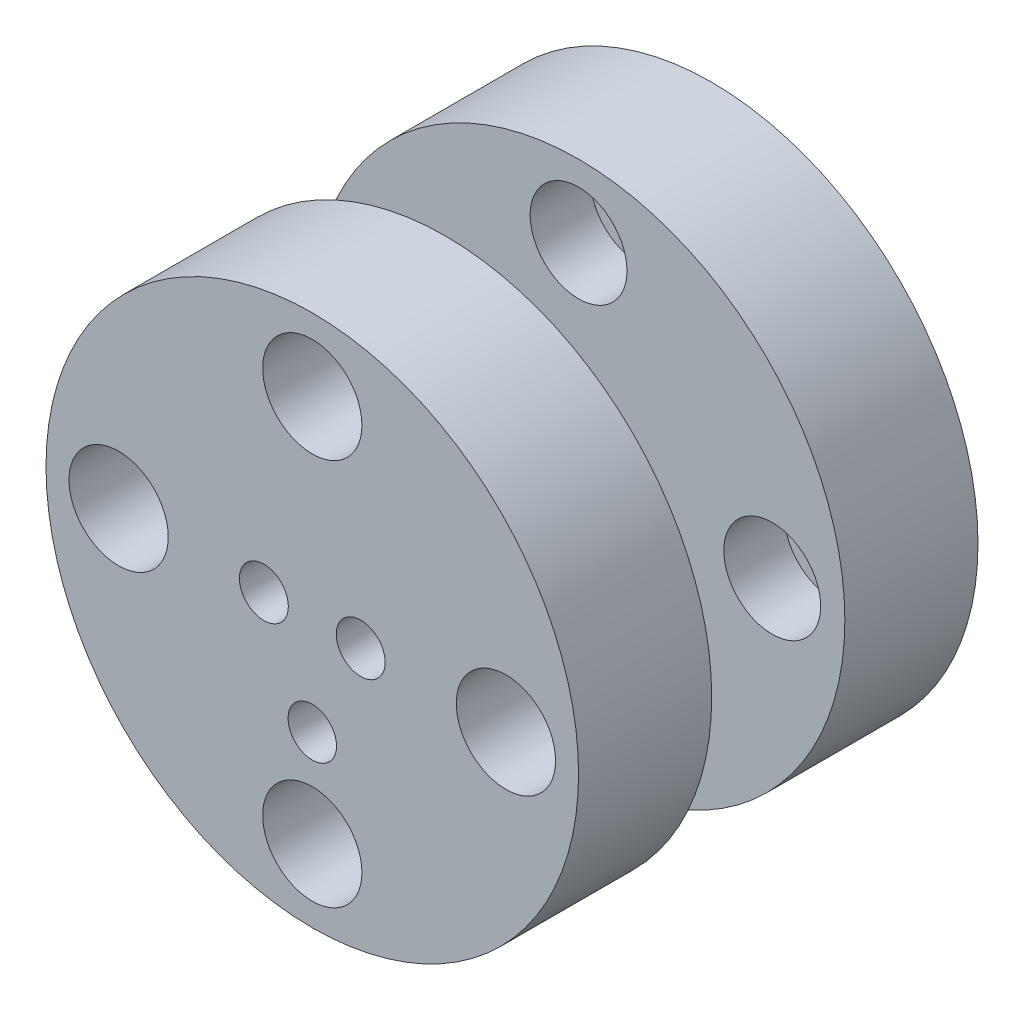
SolidWorks part; units mm, degrees
material "ﾎﾟﾘｵｷｼﾒﾁﾚﾝ(POM)ｱｾﾀｰﾙ共重合体"
ref_plane "正面" through (0, 0, 0) normal (0, 0, 1) x (1, 0, 0)
ref_plane "平面" through (0, 0, 0) normal (0, 1, 0) x (1, 0, 0)
ref_plane "右側面" through (0, 0, 0) normal (1, 0, 0) x (0, 0, -1)
sketch "ｽｹｯﾁ1" plane through (0, 0, 0) normal (0, 0, 1) x (1, 0, 0)
  line L0 (0, 0) -> (-8, 0) construction
  circle A0 centre (-8, 0) radius 1.15
  circle A1 centre (0, 8) radius 1.15
  circle A2 centre (8, 0) radius 1.15
  circle A3 centre (0, -8) radius 1.15
  circle A4 centre (0, 0) radius 11
  circle A5 centre (0, 0) radius 3 construction
  point P13 (0, 0)
  dimension "D1" = 2.3
  dimension "D4" = 8
  dimension "D5" = 6
  dimension "D2" = 8
  dimension "D3" = 4
extrude "ﾎﾞｽ - 押し出し1" add sketch "ｽｹｯﾁ1" along normal blind 5.5
sketch "ｽｹｯﾁ2" plane through (0, 0, 5.5) normal (0, 0, 1) x (1, 0, 0)
  circle A0 centre (0, 0) radius 3
  dimension "D1" = 6
extrude "ﾎﾞｽ - 押し出し2" add sketch "ｽｹｯﾁ2" along normal blind 5.5 separate body
sketch "ｽｹｯﾁ3" plane through (0, 0, 11) normal (0, 0, 1) x (1, 0, 0)
  circle A0 centre (0, 0) radius 11 construction
  circle A2 centre (0, 0) radius 11
  circle A10 centre (-8, 0) radius 2.05
  circle A11 centre (0, 8) radius 2.05
  circle A12 centre (8, 0) radius 2.05
  circle A13 centre (0, -8) radius 2.05
  point P14 (0, 0)
  dimension "D2" = 4.1
  dimension "D3" = 4
extrude "ﾎﾞｽ - 押し出し3" add sketch "ｽｹｯﾁ3" along normal blind 5.5 separate body
sketch "ｽｹｯﾁ8" plane through (0, 0, 16.5) normal (0, 0, 1) x (1, 0, 0)
  line L0 (0, 3) -> (0, 0) construction
  line L1 (0, 0) -> (-2, 0) construction
  circle A0 centre (0, 0) radius 3 construction
  circle A1 centre (-2, 0) radius 1.01
  circle A2 centre (2, 0) radius 1.01
  dimension "D1" = 6
  dimension "D2" = 2
  dimension "D3" = 2.02
extrude "ｶｯﾄ - 押し出し4" cut sketch "ｽｹｯﾁ8" against normal up to surface (11 mm away) up to face at (9.15, 0, 5.5)
sketch "ｽｹｯﾁ9" plane through (0, 0, 5.5) normal (0, 0, 1) x (1, 0, 0)
  circle A0 centre (-2, 0) radius 0.8
  circle A1 centre (2, 0) radius 0.8
  dimension "D1" = 1.6
extrude "ｶｯﾄ - 押し出し5" cut sketch "ｽｹｯﾁ9" against normal up to surface (5.5 mm away) up to face at (11, 0, 0)
sketch "ｽｹｯﾁ11" plane through (0, 0, 16.5) normal (0, 0, 1) x (1, 0, 0)
  line L0 (-2, 0) -> (2, 0) construction
  line L1 (-2, 2.5) -> (2, 2.5)
  line L2 (-2, -2.5) -> (2, -2.5)
  arc A0 (-2, 2.5) -> (-2, -2.5) centre (-2, 0) ccw
  arc A1 (2, -2.5) -> (2, 2.5) centre (2, 0) ccw
  point P4 (0, 0)
  dimension "D1" = 2.5
extrude "ｶｯﾄ - 押し出し6" [suppressed] cut sketch "ｽｹｯﾁ11" against normal offset from surface 12 and the other way blind 2.5
sketch "ｽｹｯﾁ12" plane through (0, 0, 5.5) normal (0, 0, 1) x (1, 0, 0)
  circle A0 centre (-8, 0) radius 2
  circle A1 centre (0, 8) radius 2
  circle A2 centre (8, 0) radius 2
  circle A3 centre (0, -8) radius 2
  circle A4 centre (0, 8) radius 1.15 construction
  point P4 (0, 0)
  point P11 (0, 0)
  dimension "D1" = 4
  dimension "D2" = 4
extrude "ｶｯﾄ - 押し出し7" cut sketch "ｽｹｯﾁ12" against normal blind 2.5
sketch "ｽｹｯﾁ13" plane through (0, 0, 16.5) normal (0, 0, 1) x (1, 0, 0)
  line L0 (0, 0) -> (0, -4) construction
  arc A0 (-2.995, -0.1736) -> (2.995, -0.1736) centre (0, 0) ccw construction
  arc A1 (-2.995, -0.1736) -> (2.995, -0.1736) centre (0, 0) ccw construction
  circle A2 centre (0, -4) radius 1
  dimension "D1" = 2
extrude "ｶｯﾄ - 押し出し8" cut sketch "ｽｹｯﾁ13" against normal up to surface (5.5 mm away) up to face at (-0.99, 0, 11)
